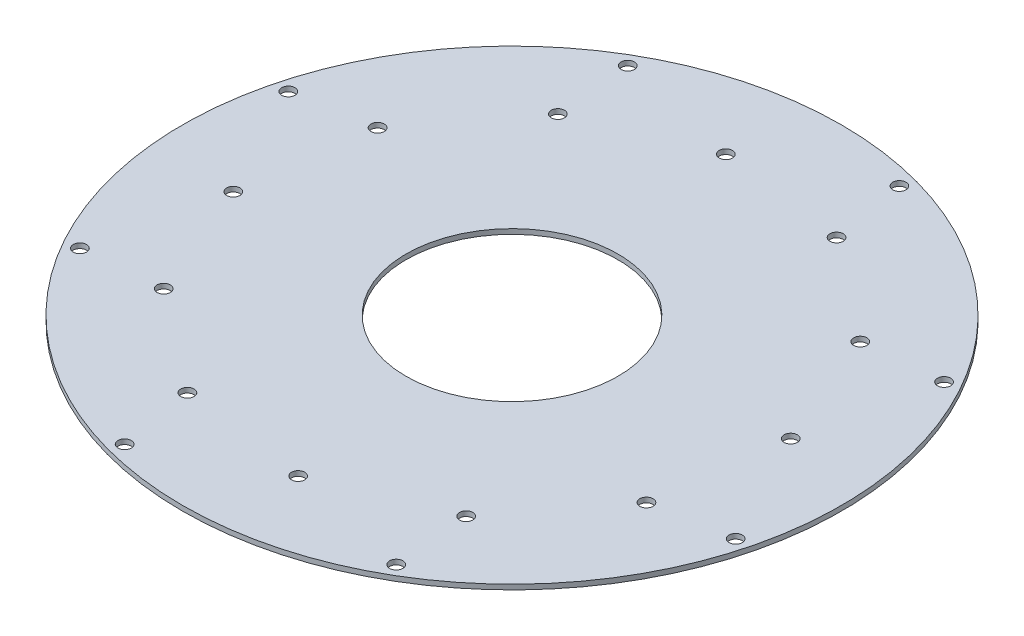
SolidWorks part; units mm, degrees
material "Thornel Mat VMA"
ref_plane "Front Plane" through (0, 0, 0) normal (0, 0, 1) x (1, 0, 0)
ref_plane "Top Plane" through (0, 0, 0) normal (0, 1, 0) x (1, 0, 0)
ref_plane "Right Plane" through (0, 0, 0) normal (1, 0, 0) x (0, 0, -1)
sketch "Sketch1" plane through (0, 0, 0) normal (0, 1, 0) x (1, 0, 0)
  circle A0 centre (0, 0) radius 32
  circle A1 centre (0, 0) radius 99.5
  dimension "D1" = 64
  dimension "D2" = 199
extrude "Base" add sketch "Sketch1" along normal mid plane 1.5
sketch "Sketch2" plane through (0, 0.75, 0) normal (0, 1, 0) x (1, 0, 0)
  line L0 (24.7172, 92.2459) -> (25.7525, 96.1096) construction
  line L1 (24.7172, 92.2459) -> (0, 0) construction
  line L2 (0, 0) -> (0, 99.5) construction
  circle A0 centre (24.7172, 92.2459) radius 2
  circle A2 centre (0, 0) radius 99.5 construction
  dimension "D1" = 4
  dimension "D2" = 4
  dimension "D3" = 15
extrude "Structural Hole" cut sketch "Sketch2" against normal through all
pattern_circular "Structural Hole Pattern" count 8 over 360 about axis through (0, 0.75, 0) along (0, -1, 0) of "Structural Hole" reverse direction yes
sketch "Sketch3" plane through (0, 0.75, 0) normal (0, 1, 0) x (1, 0, 0)
  line L0 (0, 0) -> (-9.7895, 74.3584) construction
  line L1 (0, 0) -> (0, 99.5) construction
  circle A0 centre (0, 0) radius 99.5 construction
  circle A1 centre (-9.7895, 74.3584) radius 2
  dimension "D3" = 4
  dimension "D1" = 7.5
  dimension "D2" = 75
extrude "Cut-Extrude1" cut sketch "Sketch3" against normal through all
pattern_circular "CirPattern1" count 12 over 360 about axis through (0, 0.75, 0) along (0, 1, 0) of "Cut-Extrude1"
equation "\"lift_fan_diameter\"=64"
equation "\"D1@Sketch1\"=\"lift_fan_diameter\""
equation "\"outer_diameter\"=199"
equation "\"D2@Sketch1\"=\"outer_diameter\""
equation "\"bolt_diameter\"=4"
equation "\"D1@Sketch2\"=\"bolt_diameter\""
equation "\"wall_thickness\"= 4"
equation "\"D2@Sketch2\"=\"wall_thickness\""
